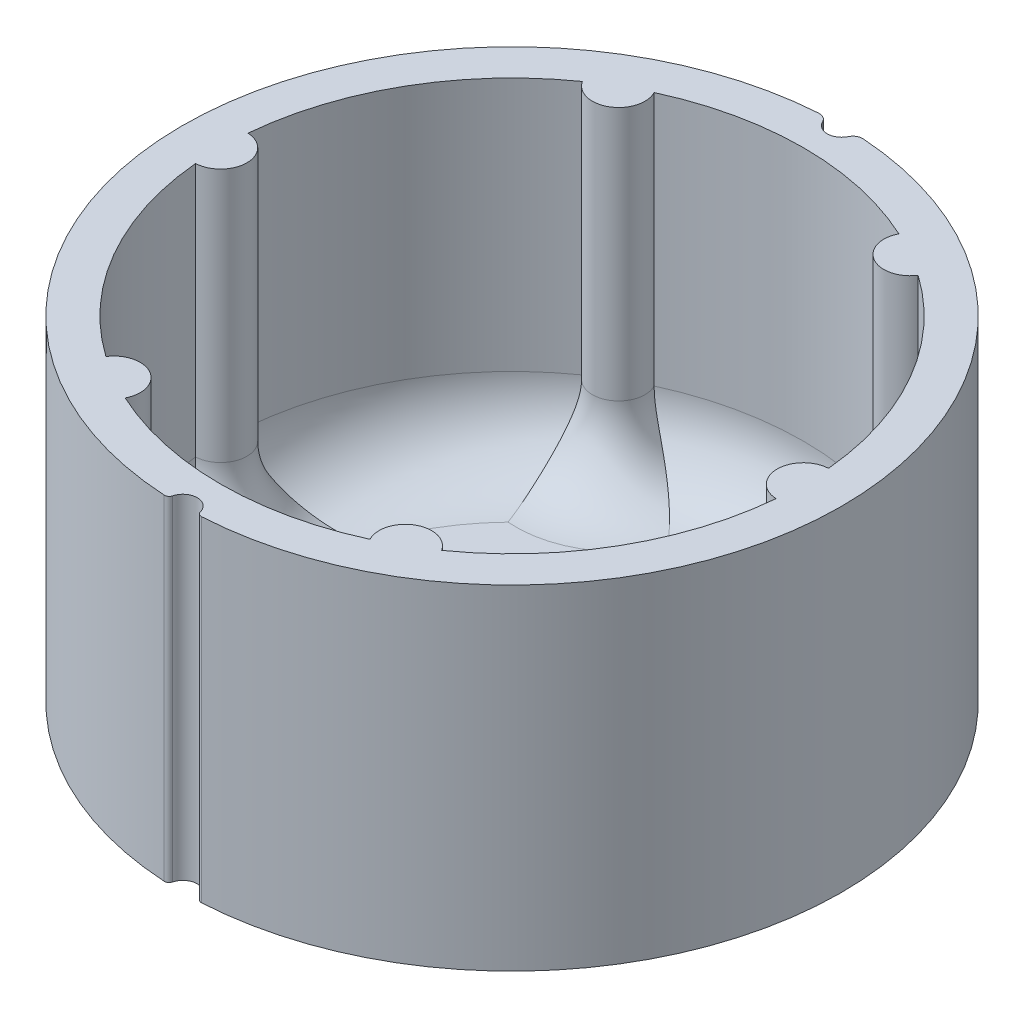
SolidWorks part; units mm, degrees
ref_plane "Front Plane" through (0, 0, 0) normal (0, 0, 1) x (1, 0, 0)
ref_plane "Top Plane" through (0, 0, 0) normal (0, 1, 0) x (1, 0, 0)
ref_plane "Right Plane" through (0, 0, 0) normal (1, 0, 0) x (0, 0, -1)
sketch "Sketch1" plane through (0, 0, 0) normal (0, 1, 0) x (1, 0, 0)
  line L3 (0, 0.002) -> (0, 3.7877) construction
  line L4 (0, 3.7877) -> (2.417, 3.7877)
  line L5 (0, 3.7877) -> (-2.417, 3.7877)
  arc A0 (1.9642, -34.442) -> (34.1982, 4.5552) centre (0, 0.002) ccw
  arc A2 (-2.417, 3.7877) -> (2.417, 3.7877) centre (0, 0.002) ccw
  circle A3 centre (0, 0.002) radius 34.5 construction
  arc A7 (-1.3541, 33.8562) -> (1.3541, 33.8562) centre (0, 34.5015) ccw
  arc A8 (34.1982, 4.5552) -> (2.3241, 34.4236) centre (0, 0.002) ccw
  arc A9 (-2.3241, 34.4236) -> (-34.1982, 4.5552) centre (0, 0.002) ccw
  arc A10 (-34.1982, 4.5552) -> (-1.9642, -34.442) centre (0, 0.002) ccw
  arc A11 (1.3541, 33.8562) -> (2.3241, 34.4236) centre (2.2568, 33.4259) cw
  arc A12 (-1.3541, 33.8562) -> (-2.3241, 34.4236) centre (-2.2568, 33.4259) ccw
  arc A13 (1.4518, -34.0686) -> (-1.4518, -34.0686) centre (0, -34.4457) ccw
  arc A14 (1.4518, -34.0686) -> (1.9642, -34.442) centre (1.9358, -33.9428) ccw
  arc A15 (-1.4518, -34.0686) -> (-1.9642, -34.442) centre (-1.9358, -33.9428) cw
  point P15 (1.4997, 34.4694)
  dimension "D2" = 4.834
  dimension "D3" = 4.4915
  dimension "D4" = 34.5
  dimension "D5" = 1
  dimension "D6" = 1.5
  dimension "D7" = 0.5
  dimension "D11" = 1.4997
sketch "Sketch2" plane through (0, 0, 0) normal (0, 1, 0) x (1, 0, 0)
  arc A16 (-17.5672, 24.9328) -> (-30.376, 2.7472) centre (0, 0) ccw
  circle A23 centre (0, 0) radius 27.75 construction
  arc A24 (30.376, 2.7472) -> (30.376, -2.7472) centre (30.5, 0) ccw
  arc A25 (17.5672, -24.9328) -> (12.8089, -27.68) centre (15.25, -26.4138) ccw
  arc A26 (-12.8089, -27.68) -> (-17.5672, -24.9328) centre (-15.25, -26.4138) ccw
  arc A27 (-30.376, -2.7472) -> (-30.376, 2.7472) centre (-30.5, 0) ccw
  arc A28 (-17.5672, 24.9328) -> (-12.8089, 27.68) centre (-15.25, 26.4138) ccw
  arc A29 (12.8089, 27.68) -> (17.5672, 24.9328) centre (15.25, 26.4138) ccw
  arc A30 (12.8089, 27.68) -> (-12.8089, 27.68) centre (0, 0) ccw
  arc A31 (30.376, 2.7472) -> (17.5672, 24.9328) centre (0, 0) ccw
  arc A32 (17.5672, -24.9328) -> (30.376, -2.7472) centre (0, 0) ccw
  arc A33 (-12.8089, -27.68) -> (12.8089, -27.68) centre (0, 0) ccw
  arc A34 (-30.376, -2.7472) -> (-17.5672, -24.9328) centre (0, 0) ccw
  point P4 (0, 0)
  point P8 (0, 0)
  point P9 (0, 0)
  point P24 (0, 0)
  point P25 (0, 0)
  point P26 (0, 0)
  point P27 (0, 0)
  dimension "D1" = 61
  dimension "D2" = 55.5
  dimension "D3" = 6
extrude "Boss-Extrude1" add sketch "Sketch1" along normal blind 35 contours A10 A0 A8 A7 A9 A2 L5 L4 region at (2.2155, 0, 33.5591)
extrude "Cut-Extrude2" cut sketch "Sketch2" along normal through all
extrude "Boss-Extrude2" add sketch "Sketch2<2>" along normal blind 0.4
sketch "Sketch2<2>" plane through (0, 0, 0) normal (0, 1, 0) x (1, 0, 0) same geometry as "Sketch2"
fillet "Fillet1" radius 8 12 edges at (13.875, 0.4, 24.0322) (0, 0.4, 30.5) (-13.875, 0.4, 24.0322) (-26.4138, 0.4, 15.25) (-27.75, 0.4, 0) (-26.4138, 0.4, -15.25) (-13.875, 0.4, -24.0322) (0, 0.4, -30.5) (13.875, 0.4, -24.0322) (26.4138, 0.4, -15.25) (27.75, 0.4, 0) (26.4138, 0.4, 15.25)
equation "\"2.5.00mm\"=3"
